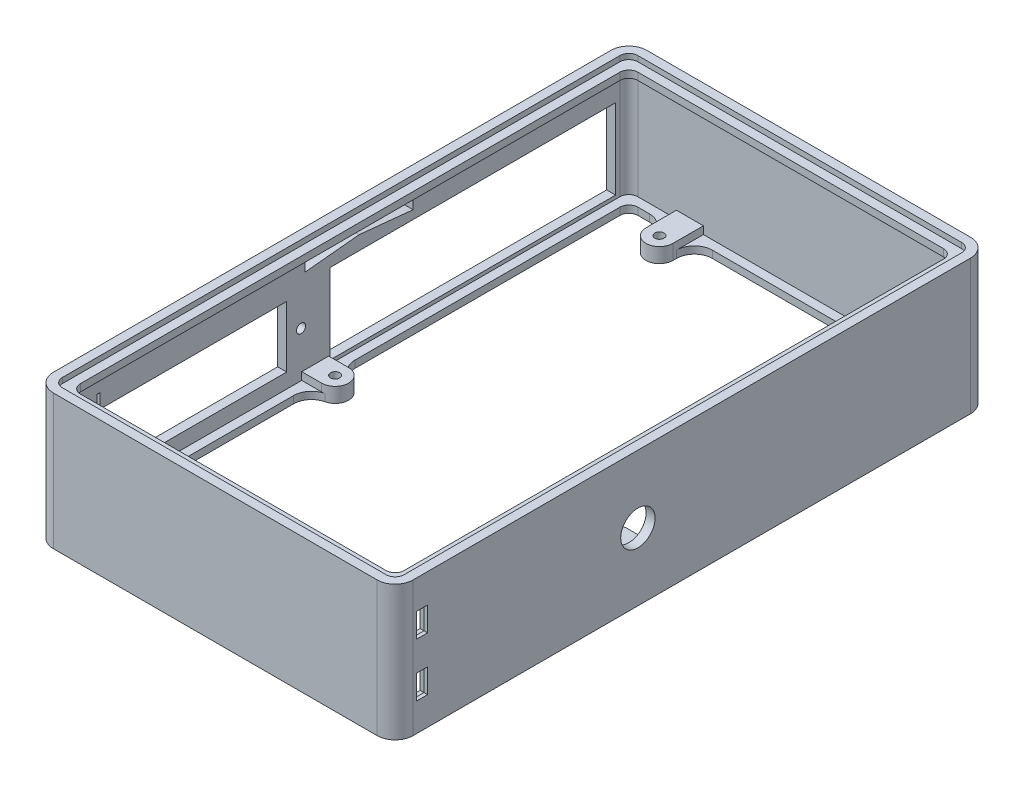
SolidWorks part; units mm, degrees
ref_plane "Front Plane" through (0, 0, 0) normal (0, 0, 1) x (1, 0, 0)
ref_plane "Top Plane" through (0, 0, 0) normal (0, 1, 0) x (1, 0, 0)
ref_plane "Right Plane" through (0, 0, 0) normal (1, 0, 0) x (0, 0, -1)
sketch "Sketch1" plane through (0, 0, 0) normal (0, 1, 0) x (1, 0, 0)
  line L1 (0, 0) -> (200, 0)
  line L2 (0, 0) -> (0, 330)
  line L3 (0, 330) -> (200, 330)
  line L4 (200, 0) -> (200, 330)
extrude "Boss-Extrude1" add sketch "Sketch1" along normal blind 75
fillet "Fillet1" radius 10 4 edges at (0, 37.5, -330) (200, 37.5, -330) (0, 37.5, 0) (200, 37.5, 0)
sketch "Sketch2" plane through (0, 75, 0) normal (0, 1, 0) x (1, 0, 0)
  line L8 (190, 325) -> (10, 325)
  line L9 (5, 320) -> (5, 10)
  line L10 (10, 5) -> (190, 5)
  line L11 (195, 10) -> (195, 320)
  line L12 (190, 325) -> (10, 325)
  line L13 (5, 320) -> (5, 10)
  line L14 (10, 5) -> (190, 5)
  line L15 (195, 10) -> (195, 320)
  arc A8 (10, 325) -> (5, 320) centre (10, 320) ccw
  arc A9 (5, 10) -> (10, 5) centre (10, 10) ccw
  arc A10 (190, 5) -> (195, 10) centre (190, 10) ccw
  arc A11 (195, 320) -> (190, 325) centre (190, 320) ccw
  arc A12 (10, 325) -> (5, 320) centre (10, 320) ccw
  arc A13 (5, 10) -> (10, 5) centre (10, 10) ccw
  arc A14 (190, 5) -> (195, 10) centre (190, 10) ccw
  arc A15 (195, 320) -> (190, 325) centre (190, 320) ccw
  dimension "D1" = 5
extrude "Cut-Extrude1" cut sketch "Sketch2" against normal blind 75
ref_plane "Plane1" through (0, 72, 0) normal (0, 1, 0) x (1, 0, 0)
ref_plane "Plane2" through (0, 3, 0) normal (0, -1, 0) x (-1, 0, 0)
sketch "Sketch3" plane through (0, 72, 0) normal (0, 1, 0) x (1, 0, 0)
  line L0 (10, 5) -> (190, 5) construction
  line L1 (195, 10) -> (195, 320) construction
  line L2 (5, 320) -> (5, 10) construction
  line L3 (190, 325) -> (10, 325) construction
  line L4 (10, 5) -> (190, 5)
  line L5 (195, 10) -> (195, 320)
  line L6 (5, 320) -> (5, 10)
  line L7 (190, 325) -> (10, 325)
  line L8 (10, 10) -> (190, 10)
  line L9 (190, 10) -> (190, 320)
  line L10 (190, 320) -> (10, 320)
  line L11 (10, 320) -> (10, 10)
  arc A0 (5, 10) -> (10, 5) centre (10, 10) ccw construction
  arc A1 (190, 5) -> (195, 10) centre (190, 10) ccw construction
  arc A2 (195, 320) -> (190, 325) centre (190, 320) ccw construction
  arc A3 (10, 325) -> (5, 320) centre (10, 320) ccw construction
  arc A4 (5, 10) -> (10, 5) centre (10, 10) ccw
  arc A5 (190, 5) -> (195, 10) centre (190, 10) ccw
  arc A6 (195, 320) -> (190, 325) centre (190, 320) ccw
  arc A7 (10, 325) -> (5, 320) centre (10, 320) ccw
  arc A8 (10, 10) -> (10, 10) centre (10, 10) ccw
  arc A9 (190, 10) -> (190, 10) centre (190, 10) ccw
  arc A10 (190, 320) -> (190, 320) centre (190, 320) ccw
  arc A11 (10, 320) -> (10, 320) centre (10, 320) ccw
  dimension "D1" = 5
extrude "Boss-Extrude2" add sketch "Sketch3" against normal blind 4
sketch "Sketch4" plane through (0, 3, 0) normal (0, -1, 0) x (-1, 0, 0)
  line L0 (-190, 320) -> (-190, 10)
  line L1 (-190, 10) -> (-10, 10)
  line L2 (-10, 10) -> (-10, 320)
  line L3 (-10, 320) -> (-190, 320)
  line L4 (-5, 10) -> (-5, 320)
  line L5 (-10, 325) -> (-190, 325)
  line L6 (-195, 320) -> (-195, 10)
  line L7 (-190, 5) -> (-10, 5)
  line L8 (-5, 10) -> (-5, 320)
  line L9 (-10, 325) -> (-190, 325)
  line L10 (-195, 320) -> (-195, 10)
  line L11 (-190, 5) -> (-10, 5)
  arc A0 (-190, 10) -> (-190, 10) centre (-190, 10) ccw
  arc A1 (-10, 10) -> (-10, 10) centre (-10, 10) ccw
  arc A2 (-10, 320) -> (-10, 320) centre (-10, 320) ccw
  arc A3 (-190, 320) -> (-190, 320) centre (-190, 320) ccw
  arc A4 (-10, 5) -> (-5, 10) centre (-10, 10) ccw
  arc A5 (-5, 320) -> (-10, 325) centre (-10, 320) ccw
  arc A6 (-190, 325) -> (-195, 320) centre (-190, 320) ccw
  arc A7 (-195, 10) -> (-190, 5) centre (-190, 10) ccw
  arc A8 (-10, 5) -> (-5, 10) centre (-10, 10) ccw
  arc A9 (-5, 320) -> (-10, 325) centre (-10, 320) ccw
  arc A10 (-190, 325) -> (-195, 320) centre (-190, 320) ccw
  arc A11 (-195, 10) -> (-190, 5) centre (-190, 10) ccw
  dimension "D1" = 0
  dimension "D2" = 5
extrude "Boss-Extrude3" add sketch "Sketch4" against normal blind 4
sketch "Sketch8" plane through (5, 0, 0) normal (1, 0, 0) x (0, 0, -1)
  line L0 (320, 7) -> (317.62, 7)
  line L1 (10, 7) -> (320, 7) construction
  line L2 (317.62, 7) -> (317.62, 9)
  line L3 (317.62, 9) -> (317.62, 53.5)
  line L4 (317.62, 53.5) -> (158.87, 53.5)
  line L6 (158.87, 53.5) -> (317.62, 53.5)
  line L7 (158.87, 53.5) -> (158.87, 9)
  line L8 (158.87, 9) -> (317.62, 9)
  line L9 (317.62, 53.5) -> (317.62, 9)
extrude "Cut-Extrude2" cut sketch "Sketch8" against normal blind 40 contours L7 L8 L3 L4 region at (5, 31.25, -238.245)
sketch "Sketch11" plane through (0, 3, 0) normal (0, -1, 0) x (1, 0, 0)
  line L1 (16.06, -158.09) -> (10, -158.09)
  line L2 (10, -10) -> (10, -320) construction
  line L4 (10, -143.09) -> (16.06, -143.09)
  line L5 (31.42, -308.07) -> (31.42, -320)
  line L6 (10, -320) -> (190, -320) construction
  line L8 (46.42, -320) -> (46.42, -308.07)
  line L9 (171, -300.57) -> (190, -300.57)
  line L10 (190, -320) -> (190, -10) construction
  line L13 (163.5, -320) -> (163.5, -308.07)
  line L14 (171, -158.09) -> (190, -158.09)
  line L16 (190, -143.09) -> (171, -143.09)
  line L17 (190, -158.09) -> (195, -158.09)
  line L18 (195, -10) -> (195, -320) construction
  line L19 (195, -158.09) -> (195, -143.09)
  line L20 (195, -320) -> (195, -10) construction
  line L21 (195, -143.09) -> (190, -143.09)
  line L22 (190, -300.57) -> (195, -300.57)
  line L23 (195, -300.57) -> (195, -320)
  line L24 (163.5, -320) -> (163.5, -325)
  line L25 (190, -325) -> (10, -325) construction
  line L26 (163.5, -325) -> (190, -325)
  line L27 (5, -10) -> (5, -320) construction
  line L29 (46.42, -320) -> (46.42, -325)
  line L30 (46.42, -325) -> (31.42, -325)
  line L31 (31.42, -320) -> (31.42, -325)
  line L32 (10, -158.09) -> (5, -158.09)
  line L34 (10, -143.09) -> (5, -143.09)
  line L35 (5, -158.09) -> (5, -143.09)
  circle A0 centre (38.92, -308.07) radius 2.55
  circle A1 centre (171, -308.07) radius 2.55
  circle A2 centre (171, -150.59) radius 2.55
  circle A3 centre (16.06, -150.59) radius 2.55
  arc A4 (16.06, -158.09) -> (16.06, -143.09) centre (16.06, -150.59) ccw
  arc A5 (171, -143.09) -> (171, -158.09) centre (171, -150.59) ccw
  arc A6 (171, -300.57) -> (163.5, -308.07) centre (171, -308.07) ccw
  arc A7 (46.42, -308.07) -> (31.42, -308.07) centre (38.92, -308.07) ccw
  arc A8 (190, -325) -> (195, -320) centre (190, -320) ccw construction
  arc A9 (190, -325) -> (195, -320) centre (190, -320) ccw
extrude "Boss-Extrude4" add sketch "Sketch11" against normal blind 8.23
sketch "Sketch12" plane through (0, 0, 0) normal (-1, 0, 0) x (0, 0, 1)
  line L0 (-134.7, 32.25) -> (-142.7, 32.25)
  line L4 (-134.7, 15.25) -> (-32.9, 15.25)
  line L5 (-134.7, 15.25) -> (-134.7, 49.25)
  line L6 (-134.7, 49.25) -> (-32.9, 49.25)
  line L7 (-32.9, 49.25) -> (-32.9, 15.25)
  circle A0 centre (-142.7, 32.25) radius 2.55
extrude "Cut-Extrude3" cut sketch "Sketch12" against normal blind 31.23 contours L7 L6 L5 L4 | A0 region at (0, 32.25, -145.1779) region at (0, 32.25, -83.8)
sketch "Sketch13" plane through (195, 0, 0) normal (-1, 0, 0) x (0, 0, 1)
  line L0 (-10, 37.5) -> (-130, 37.5)
  line L1 (-10, 7) -> (-10, 68) construction
  line L2 (-10, 37.5) -> (-135, 37.5)
  circle A0 centre (-135, 37.5) radius 9.55
extrude "Cut-Extrude4" cut sketch "Sketch13" against normal blind 31.23
fillet "Fillet2" radius 10 4 edges at (31.42, 5, -320) (46.42, 5, -320) (10, 5, -143.09) (10, 5, -158.09)
fillet "Fillet3" radius 20 2 edges at (190, 5, -143.09) (190, 5, -158.09)
fillet "Fillet4" radius 5 7 edges at (10, 5, -10) (190, 5, -10) (10, 5, -320) (10, 70, -320) (190, 70, -320) (190, 70, -10) (10, 70, -10)
sketch "Sketch14" plane through (0, 0, 0) normal (-1, 0, 0) x (0, 0, 1)
  line L0 (-32.9, 15.25) -> (-30.9, 15.25)
  line L1 (-30.9, 15.25) -> (-30.9, 10.25)
  line L2 (-30.9, 10.25) -> (-29.15, 10.25)
  line L3 (-32.9, 49.25) -> (-30.9, 49.25)
  line L4 (-30.9, 49.25) -> (-30.9, 57.25)
  line L6 (-30.9, 57.25) -> (-29.15, 57.25)
  line L7 (-30.9, 57.25) -> (-30.9, 10.25)
  line L8 (-30.9, 10.25) -> (-29.15, 10.25)
  line L9 (-29.15, 57.25) -> (-29.15, 10.25)
extrude "Cut-Extrude5" cut sketch "Sketch14" against normal blind 10 contours L9 L6 L4 L7 L1 L2 region at (0, 33.75, -30.025)
sketch "Sketch15" plane through (0, 0, 0) normal (-1, 0, 0) x (0, 0, 1)
  line L1 (-30.9, 10.25) -> (-32.9, 10.25)
  line L2 (-30.9, 10.25) -> (-30.9, 57.2714)
  line L3 (-30.9, 57.2714) -> (-32.9, 57.2714)
  line L4 (-32.9, 10.25) -> (-32.9, 57.2714)
extrude "Boss-Extrude5" add sketch "Sketch15" along normal blind 8
sketch "Sketch16" plane through (0, 0, -32.9) normal (0, 0, -1) x (-1, 0, 0)
  line L0 (0, 15.25) -> (0.5, 15.25)
  line L1 (0.5, 15.25) -> (0.5, 31.75)
  circle A0 centre (0.5, 31.75) radius 2.55
extrude "Cut-Extrude6" cut sketch "Sketch16" against normal blind 2 contours A0 region at (-2.2521, 29.9979, -32.9)
sketch "Sketch17" plane through (0, 0, -32.9) normal (0, 0, -1) x (-1, 0, 0)
  circle A0 centre (0.5, 31.75) radius 4.5
  circle A1 centre (0.5, 31.75) radius 2.55
extrude "Boss-Extrude6" add sketch "Sketch17" along normal blind 3
chamfer "Chamfer1" distance 3 angle 45 1 edges at (-5, 31.75, -32.9)
fillet "Fillet5" radius 5 2 edges at (-8, 57.2714, -31.9) (-8, 10.25, -31.9)
chamfer "Chamfer2" distance 3 angle 45 2 edges at (0, 53.2607, -32.9) (0, 12.75, -32.9)
sketch "Sketch19" plane through (200, 0, 0) normal (1, 0, 0) x (0, 0, -1)
  line L0 (5, 7) -> (5, 68) construction
  line L1 (5, 7) -> (5, 68)
  line L2 (5, 37.5) -> (25, 37.5)
  line L3 (15, 37.5) -> (15, 52)
  line L4 (15, 52) -> (15, 22.25)
  line L5 (15, 52) -> (15, 44.75)
  line L6 (15, 44.75) -> (18.5, 44.75)
  line L7 (15, 22.25) -> (15, 29.5)
  line L8 (18.5, 44.75) -> (11.5, 44.75)
  line L9 (18.5, 44.75) -> (18.5, 59.25)
  line L10 (18.5, 59.25) -> (11.5, 59.25)
  line L11 (11.5, 44.75) -> (11.5, 59.25)
  line L12 (15, 29.5) -> (18.5, 29.5)
  line L14 (18.5, 29.5) -> (11.5, 29.5)
  line L15 (18.5, 29.5) -> (18.5, 15)
  line L16 (18.5, 15) -> (11.5, 15)
  line L17 (11.5, 29.5) -> (11.5, 15)
extrude "Cut-Extrude8" cut sketch "Sketch19" against normal blind 18 contours L11 L8 L6 L9 L10 | L14 L17 L16 L15 L12 region at (200, 44.911, -13.25) region at (200, 29.339, -16.75)
sketch "Sketch20" plane through (0, 0, -5) normal (0, 0, -1) x (-1, 0, 0)
  line L0 (-195, 29.5) -> (-195, 15) construction
  line L1 (-195, 29.5) -> (-195, 15)
  line L2 (-195, 20.2001) -> (-188, 20.2001)
  line L3 (-188, 20.2001) -> (-185, 20.2001)
  line L4 (-195, 44.75) -> (-195, 59.25) construction
  line L5 (-195, 44.75) -> (-195, 59.25)
  line L6 (-195, 29.5) -> (-195, 15)
  line L7 (-195, 29.5) -> (-195, 44.75)
  line L8 (-195, 15) -> (-185, 15)
  line L9 (-185, 37.125) -> (-185, 62.125)
  line L10 (-180, 37.125) -> (-178, 37.125)
  line L11 (-185, 37.125) -> (-185, 12.125)
  line L12 (-185, 12.125) -> (-170, 12.125)
  line L13 (-185, 59.25) -> (-170, 59.25)
  line L14 (-185, 62.125) -> (-170, 62.125)
  circle A0 centre (-178, 37.125) radius 2.55
  circle A1 centre (-168, 62.125) radius 2.55
  circle A2 centre (-168, 12.125) radius 2.55
sketch "Sketch22" plane through (200, 0, 0) normal (1, 0, 0) x (0, 0, -1)
  line L0 (11.5, 44.75) -> (11.5, 59.25) construction
  line L1 (18.5, 59.25) -> (11.5, 59.25)
  line L2 (18.5, 59.25) -> (18.5, 59.625)
  line L3 (18.5, 59.625) -> (11.5, 59.625)
  line L4 (11.5, 59.25) -> (11.5, 59.625)
  line L5 (11.5, 29.5) -> (11.5, 15) construction
  line L6 (18.5, 29.5) -> (11.5, 29.5)
  line L7 (18.5, 29.5) -> (18.5, 29.875)
  line L8 (18.5, 29.875) -> (11.5, 29.875)
  line L9 (11.5, 29.5) -> (11.5, 29.875)
extrude "Cut-Extrude9" cut sketch "Sketch22" against normal blind 18
sketch "Sketch23" plane through (200, 0, 0) normal (1, 0, 0) x (0, 0, -1)
  line L0 (11.5, 44.75) -> (11.5, 59.625) construction
  line L1 (18.5, 44.75) -> (11.5, 44.75)
  line L2 (18.5, 44.75) -> (18.5, 45.125)
  line L3 (18.5, 45.125) -> (11.5, 45.125)
  line L4 (11.5, 44.75) -> (11.5, 45.125)
  line L5 (11.5, 29.875) -> (11.5, 15) construction
  line L6 (18.5, 15) -> (11.5, 15)
  line L7 (18.5, 15) -> (18.5, 15.375)
  line L8 (18.5, 15.375) -> (11.5, 15.375)
  line L9 (11.5, 15) -> (11.5, 15.375)
extrude "Boss-Extrude7" add sketch "Sketch23" against normal up to surface (5 mm away) up to face at (195, 52.1875, -15)
extrude "Cut-Extrude10" cut sketch "Sketch20" against normal blind 18 contours A2 | A0 | A1 region at (168, 12.125, -5)
sketch "Sketch24" plane through (200, 0, 0) normal (1, 0, 0) x (0, 0, -1)
  line L23 (11, 14.875) -> (19, 14.875)
  line L24 (11, 30.375) -> (11, 14.875)
  line L25 (19, 30.375) -> (11, 30.375)
  line L26 (19, 14.875) -> (19, 30.375)
  line L27 (11, 14.875) -> (19, 14.875)
  line L28 (11, 30.375) -> (11, 14.875)
  line L29 (19, 30.375) -> (11, 30.375)
  line L30 (19, 14.875) -> (19, 30.375)
  line L143 (19, 44.625) -> (19, 60.125)
  line L144 (11, 44.625) -> (19, 44.625)
  line L145 (11, 60.125) -> (11, 44.625)
  line L146 (19, 60.125) -> (11, 60.125)
  line L147 (19, 44.625) -> (19, 60.125)
  line L148 (11, 44.625) -> (19, 44.625)
  line L149 (11, 60.125) -> (11, 44.625)
  line L150 (19, 60.125) -> (11, 60.125)
  dimension "D1" = 0.5
  dimension "D2" = 0.5
extrude "Cut-Extrude12" cut sketch "Sketch24" against normal blind 10
sketch "Sketch25" plane through (200, 0, 0) normal (1, 0, 0) x (0, 0, -1)
  line L0 (11, 60.125) -> (11, 44.625) construction
  line L1 (19, 60.125) -> (11, 60.125)
  line L2 (19, 60.125) -> (19, 59.725)
  line L3 (19, 59.725) -> (11, 59.725)
  line L4 (11, 60.125) -> (11, 59.725)
  line L6 (19, 30.375) -> (11, 30.375)
  line L7 (19, 30.375) -> (19, 29.975)
  line L8 (19, 29.975) -> (11, 29.975)
  line L9 (11, 30.375) -> (11, 29.975)
extrude "Boss-Extrude8" add sketch "Sketch25" against normal up to surface (5 mm away) up to face at (195, 1.5, -165)
sketch "Sketch26" plane through (200, 0, 0) normal (1, 0, 0) x (0, 0, -1)
  line L1 (11, 44.625) -> (11.1, 44.625)
  line L2 (11, 44.625) -> (11, 59.725)
  line L3 (11, 59.725) -> (11.1, 59.725)
  line L4 (11.1, 44.625) -> (11.1, 59.725)
  line L9 (19, 44.625) -> (18.9, 44.625)
  line L10 (19, 44.625) -> (19, 59.725)
  line L11 (19, 59.725) -> (18.9, 59.725)
  line L12 (18.9, 44.625) -> (18.9, 59.725)
  line L17 (19, 29.975) -> (18.9, 29.975)
  line L18 (19, 29.975) -> (19, 14.875)
  line L19 (19, 14.875) -> (18.9, 14.875)
  line L20 (18.9, 29.975) -> (18.9, 14.875)
  line L25 (11, 14.875) -> (11.1, 14.875)
  line L26 (11, 14.875) -> (11, 29.975)
  line L27 (11, 29.975) -> (11.1, 29.975)
  line L28 (11.1, 14.875) -> (11.1, 29.975)
extrude "Boss-Extrude9" add sketch "Sketch26" against normal up to surface (5 mm away) up to face at (195, 1.5, -165)
sketch "Sketch27" plane through (200, 0, 0) normal (1, 0, 0) x (0, 0, -1)
  line L0 (18.9, 52.175) -> (11.1, 52.175)
  line L1 (18.9, 59.725) -> (18.9, 44.625) construction
  line L2 (11.1, 44.625) -> (11.1, 59.725) construction
  line L3 (11.1, 52.175) -> (15, 52.175)
  line L4 (15, 52.175) -> (15, 58.875)
  line L5 (15, 58.875) -> (18.05, 58.875)
  line L6 (18.9, 22.425) -> (11.1, 22.425)
  line L7 (18.05, 58.875) -> (11.95, 58.875)
  line L8 (18.05, 58.875) -> (18.05, 45.475)
  line L9 (18.05, 45.475) -> (11.95, 45.475)
  line L10 (11.95, 58.875) -> (11.95, 45.475)
  line L11 (18.9, 59.725) -> (11.1, 59.725)
  line L12 (18.9, 59.725) -> (18.9, 44.625)
  line L13 (18.9, 44.625) -> (11.1, 44.625)
  line L14 (11.1, 59.725) -> (11.1, 44.625)
  line L15 (18.9, 29.975) -> (18.9, 14.875) construction
  line L16 (11.1, 14.875) -> (11.1, 29.975) construction
  line L17 (11.1, 22.425) -> (15, 22.425)
  line L18 (15, 22.425) -> (15, 29.125)
  line L19 (15, 29.125) -> (18.05, 29.125)
  line L21 (18.05, 29.125) -> (11.95, 29.125)
  line L22 (18.05, 29.125) -> (18.05, 15.725)
  line L23 (18.05, 15.725) -> (11.95, 15.725)
  line L24 (11.95, 29.125) -> (11.95, 15.725)
  line L25 (18.9, 29.975) -> (11.1, 29.975)
  line L26 (18.9, 29.975) -> (18.9, 14.875)
  line L27 (18.9, 14.875) -> (11.1, 14.875)
  line L28 (11.1, 29.975) -> (11.1, 14.875)
  line M5 (18.9, 14.875) -> (11.1, 14.875)
  line M6 (11.1, 14.875) -> (11.1, 29.975)
  line M7 (11.1, 29.975) -> (18.9, 29.975)
  line M8 (18.9, 29.975) -> (18.9, 14.875)
  line M9 (18.9, 44.625) -> (11.1, 44.625)
  line M10 (11.1, 44.625) -> (11.1, 59.725)
  line M11 (11.1, 59.725) -> (18.9, 59.725)
  line M12 (18.9, 59.725) -> (18.9, 44.625)
extrude "Boss-Extrude10" add sketch "Sketch27" against normal blind 2 contours L24 L21 L19 L22 L6 L17 M8 M7 M6 | L24 L17 L6 L22 L23 M6 M5 M8 | L10 L3 L0 L8 L9 M10 M9 M12 | L10 L7 L5 L8 L0 L3 M12 M11 M10 region at (200, 48.4, -18.7914) region at (200, 52.2836, -18.475) region at (200, 18.65, -18.7914) region at (200, 22.5336, -18.475)
sketch "Sketch28" plane through (0, 0, -5) normal (0, 0, -1) x (-1, 0, 0)
  line L1 (-183.2614, 41.5619) -> (-170.2756, 41.5619)
  line L2 (-183.2614, 41.5619) -> (-183.2614, 31.146)
  line L3 (-183.2614, 31.146) -> (-170.2756, 31.146)
  line L4 (-170.2756, 41.5619) -> (-170.2756, 31.146)
extrude "Boss-Extrude11" add sketch "Sketch28" against normal up to surface (5 mm away) up to face at (165.45, 12.125, 0)
sketch "Sketch29" plane through (0, 0, 0) normal (0, 0, 1) x (1, 0, 0)
  circle A0 centre (168, 62.125) radius 2.55
  circle A1 centre (168, 12.125) radius 2.55
extrude "Boss-Extrude12" add sketch "Sketch29" against normal blind 0.6
sketch "Sketch30" plane through (0, 75, 0) normal (0, 1, 0) x (1, 0, 0)
  line L0 (100, 330) -> (100, 0)
  line L1 (190, 330) -> (10, 330) construction
  line L2 (10, 0) -> (190, 0) construction
  line L3 (0, 175) -> (200, 175)
  line L5 (200, 10) -> (200, 320) construction
  line L8 (54.8916, 175) -> (100, 175)
  line L9 (100, 175) -> (0, 175)
  line L10 (0, 320) -> (0, 10) construction
sketch "Sketch31" plane through (0, 0, 0) normal (-1, 0, 0) x (0, 0, 1)
  line L0 (0, 75) -> (-175, 75)
  line L1 (-330, 75) -> (0, 75) construction
  line L2 (-175, 64.25) -> (-205, 64.25)
  line L4 (-175, 75) -> (-175, 53.5)
  line L5 (-317.62, 53.5) -> (-158.87, 53.5) construction
  line L6 (-175, 64.25) -> (-145, 64.25)
  line L7 (-205, 64.25) -> (-205, 70.25)
  line L8 (-205, 70.25) -> (-205, 58.25)
  line L9 (-145, 64.25) -> (-145, 58.25)
  line L10 (-145, 58.25) -> (-145, 70.25)
  line L11 (-175, 64.25) -> (-175, 61.25)
  line L12 (-175, 64.25) -> (-175, 67.25)
  line L13 (-205, 58.25) -> (-175, 61.25)
  line L14 (-145, 58.25) -> (-175, 61.25)
  line L15 (-205, 70.25) -> (-175, 67.25)
  line L16 (-175, 67.25) -> (-145, 70.25)
extrude "Cut-Extrude13" cut sketch "Sketch31" against normal up to surface (5 mm away) contours L8 L13 L4 L2 | L15 L7 L2 L4 | L14 L9 L6 L4 | L16 L4 L6 L10 region at (0, 61.9167, -191.6667) region at (0, 66.5833, -191.6667) region at (0, 61.9167, -158.3333) region at (0, 66.5833, -158.3333) up to face at (5, 32.1196, -67.1659)
